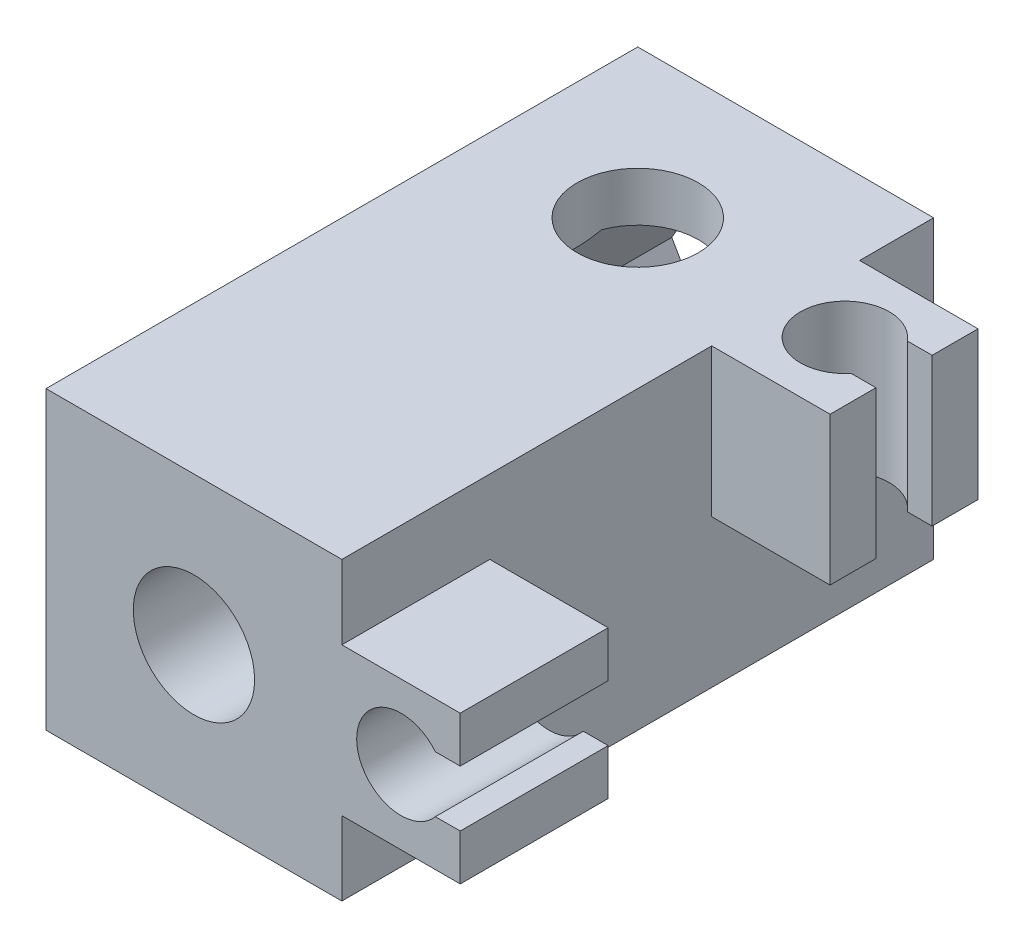
SolidWorks part; units mm, degrees
ref_plane "Спереди" through (0, 0, 0) normal (0, 0, 1) x (1, 0, 0)
ref_plane "Сверху" through (0, 0, 0) normal (0, 1, 0) x (1, 0, 0)
ref_plane "Справа" through (0, 0, 0) normal (1, 0, 0) x (0, 0, -1)
sketch "Sketch1" plane through (0, 0, 0) normal (0, 1, 0) x (1, 0, 0)
  line L1 (10, -20) -> (-10, -20)
  line L2 (10, -20) -> (10, 20)
  line L3 (10, 20) -> (-10, 20)
  line L4 (-10, -20) -> (-10, 20)
  line L5 (10, -20) -> (-10, 20) construction
  line L6 (10, 20) -> (-10, -20) construction
  point P0 (0, 0)
  dimension "D1" = 20
  dimension "D2" = 40
extrude "Boss-Extrude1" add sketch "Sketch1" along normal blind 20
sketch "Sketch2" plane through (0, 0, 0) normal (0, -1, 0) x (1, 0, 0)
  line L0 (10, -10) -> (-10, -10) construction
  line L1 (10, 20) -> (10, -20) construction
  line L2 (-10, -20) -> (-10, 20) construction
  line L3 (10, -20) -> (-10, -20) construction
  circle A0 centre (0, -10) radius 4.1
  dimension "D1" = 8.2
  dimension "D2" = 10
extrude "Cut-Extrude1" cut sketch "Sketch2" against normal through all
sketch "Sketch3" plane through (0, 0, 20) normal (0, 0, 1) x (1, 0, 0)
  line L0 (0, 0) -> (0, 20) construction
  line L1 (-10, 0) -> (10, 0) construction
  line L2 (-10, 20) -> (10, 20) construction
  circle A0 centre (0, 10) radius 4.1
  dimension "D1" = 8.2
extrude "Cut-Extrude2" cut sketch "Sketch3" against normal through all
sketch "Sketch4" plane through (0, 0, -20) normal (0, 0, -1) x (-1, 0, 0)
  line L1 (-7.7, 10) -> (-3.85, 3.3316)
  line L2 (-3.85, 3.3316) -> (3.85, 3.3316)
  line L3 (3.85, 3.3316) -> (7.7, 10)
  line L4 (7.7, 10) -> (3.85, 16.6684)
  line L5 (3.85, 16.6684) -> (-3.85, 16.6684)
  line L6 (-3.85, 16.6684) -> (-7.7, 10)
  circle A0 centre (0, 10) radius 7.7 construction
  dimension "D1" = 15.4
extrude "Cut-Extrude3" cut sketch "Sketch4" against normal blind 21
sketch "Sketch5" plane through (0, 20, 0) normal (0, 1, 0) x (1, 0, 0)
  line L0 (4.1, 10) -> (27.7656, 10) construction
  line L1 (10, -20) -> (10, 20) construction
  line L2 (18, 5) -> (10, 5)
  line L3 (18, 5) -> (18, 15) construction
  line L4 (18, 15) -> (10, 15)
  line L5 (10, 5) -> (10, 15)
  line L6 (18, 5) -> (10, 15) construction
  line L7 (18, 15) -> (10, 5) construction
  line L8 (18, 15) -> (18, 11.9)
  line L9 (18, 11.9) -> (16.3216, 11.9)
  line L10 (16.3216, 11.9) -> (16.3216, 8.1)
  line L11 (16.3216, 8.1) -> (18, 8.1)
  line L12 (18, 8.1) -> (18, 5)
  line L13 (-4.1, 10) -> (4.1, 10) construction
  circle A0 centre (0, 10) radius 4.1 construction
  circle A1 centre (14, 10) radius 3 construction
  arc A2 (16.3216, 11.9) -> (16.3216, 8.1) centre (14, 10) ccw
  point P4 (14, 10)
  point P18 (0, 0)
  line M8 (10, -20) -> (10, 20)
  dimension "D3" = 6
  dimension "D1" = 10
  dimension "D2" = 8
  dimension "D4" = 3.8
extrude "Boss-Extrude2" add sketch "Sketch5" against normal blind 10 contours A2 L9 L8 L4 L2 L12 L11 M8 region at (14, 20, -5.1281)
sketch "Sketch6" plane through (0, 0, 20) normal (0, 0, 1) x (1, 0, 0)
  line L0 (4.1, 10) -> (27.9047, 10) construction
  line L1 (10, 20) -> (10, 0) construction
  line L2 (18, 5) -> (10, 5)
  line L3 (18, 5) -> (18, 15) construction
  line L4 (18, 15) -> (10, 15)
  line L5 (10, 5) -> (10, 15)
  line L6 (18, 5) -> (10, 15) construction
  line L7 (18, 15) -> (10, 5) construction
  line L8 (18, 15) -> (18, 11.9)
  line L9 (18, 11.9) -> (16.3216, 11.9)
  line L10 (16.3216, 11.9) -> (16.3216, 8.1)
  line L11 (16.3216, 8.1) -> (18, 8.1)
  line L12 (18, 8.1) -> (18, 5)
  circle A0 centre (0, 10) radius 4.1 construction
  circle A1 centre (14, 10) radius 3 construction
  arc A2 (16.3216, 11.9) -> (16.3216, 8.1) centre (14, 10) ccw
  point P5 (14, 10)
  line M10 (10, 0) -> (10, 20)
  dimension "D3" = 6
  dimension "D1" = 8
  dimension "D2" = 10
  dimension "D4" = 3.8
extrude "Boss-Extrude3" add sketch "Sketch6" against normal blind 10 contours A2 L9 L8 L4 L2 L12 L11 M10 region at (14, 5.1281, 20)
